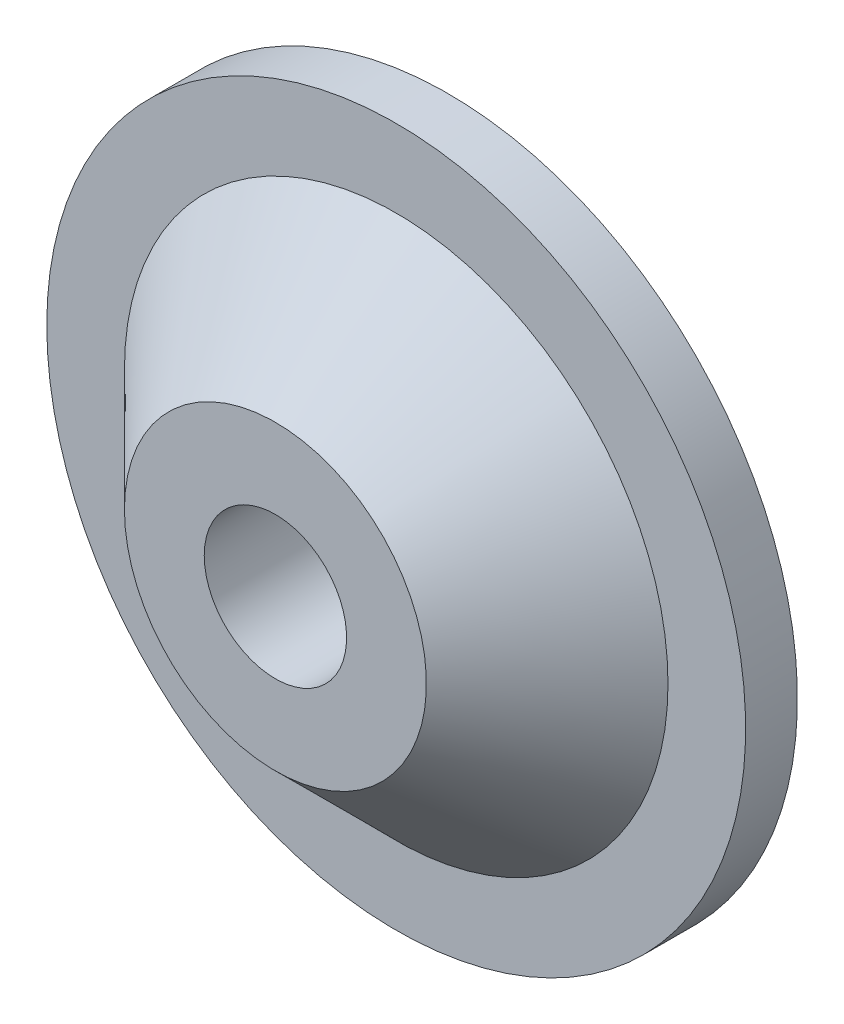
SolidWorks part; units mm, degrees
ref_plane "Front Plane" through (0, 0, 0) normal (0, 0, 1) x (1, 0, 0)
ref_plane "Top Plane" through (0, 0, 0) normal (0, 1, 0) x (1, 0, 0)
ref_plane "Right Plane" through (0, 0, 0) normal (1, 0, 0) x (0, 0, -1)
sketch "Sketch3" plane through (0, 0, 0) normal (0, 1, 0) x (1, 0, 0)
  line L0 (0, 35.5801) -> (0, 0)
  line L1 (6.3, 0) -> (8.1, 0)
  line L2 (8.1, 0) -> (8.1, 1.2)
  line L3 (8.1, 1.2) -> (1.65, 1.2)
  line L4 (1.65, 1.2) -> (1.65, 0)
  line L5 (3.5, -2.8) -> (-3.5, -2.8) construction
  line L6 (3.5, -2.8) -> (-3.5, -2.8) construction
  line L7 (1.65, 0) -> (1.65, -2.8)
  line L8 (1.65, -2.8) -> (3.5, -2.8)
  line L9 (3.5, -2.8) -> (6.3, 0)
  dimension "D1" = 8.1
  dimension "D2" = 1.65
  dimension "D3" = 1.2
revolve "Revolve1" add sketch "Sketch3" angle 360 about L0 region at (4.0647, 0, 0.3721)
equation "\"`6.4\"=107.223"
